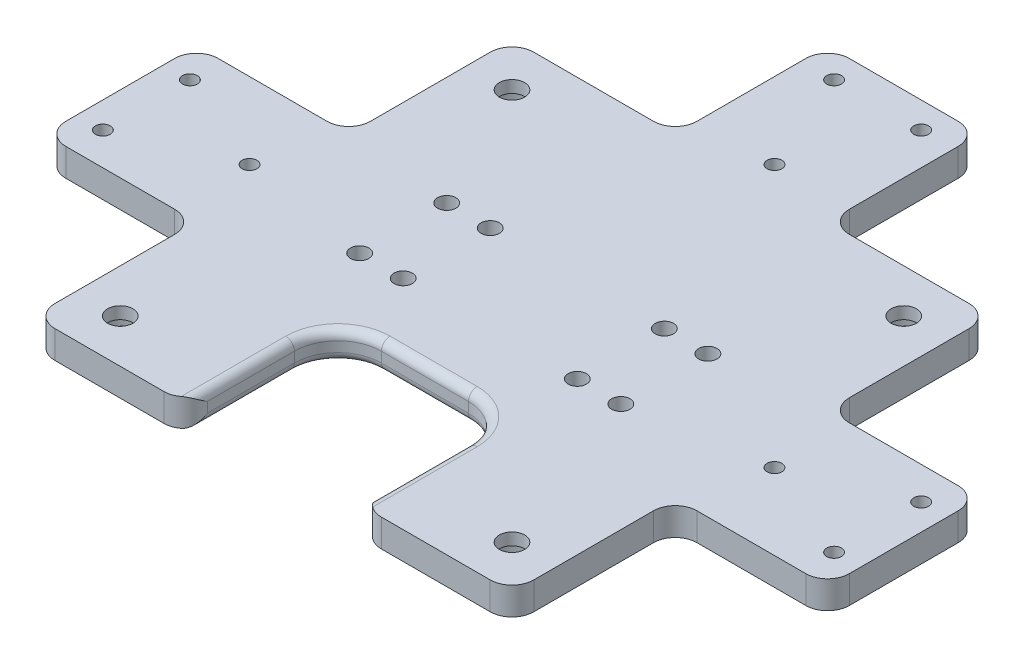
SolidWorks part; units mm, degrees
ref_plane "Front Plane" through (0, 0, 0) normal (0, 0, 1) x (1, 0, 0)
ref_plane "Top Plane" through (0, 0, 0) normal (0, 1, 0) x (1, 0, 0)
ref_plane "Right Plane" through (0, 0, 0) normal (1, 0, 0) x (0, 0, -1)
sketch "Base plate" plane through (0, 0, 0) normal (0, 1, 0) x (1, 0, 0)
  line L0 (55, -55) -> (-55, -55)
  line L5 (17.5, 55) -> (17.5, 90)
  line L6 (55, 55) -> (17.5, 55)
  line L7 (-55, -55) -> (-55, -17.5)
  line L8 (-55, -17.5) -> (-90, -17.5)
  line L9 (-90, -17.5) -> (-90, 17.5)
  line L10 (-90, 17.5) -> (-55, 17.5)
  line L11 (-55, 17.5) -> (-55, 55)
  line L12 (-55, 55) -> (-17.5, 55)
  line L13 (-17.5, 55) -> (-17.5, 90)
  line L14 (-17.5, 90) -> (17.5, 90)
  line L15 (0, 90) -> (0, -55) construction
  line L16 (55, 17.5) -> (55, 55)
  line L17 (90, 17.5) -> (55, 17.5)
  line L18 (90, -17.5) -> (90, 17.5)
  line L19 (55, -17.5) -> (90, -17.5)
  line L20 (55, -55) -> (55, -17.5)
  point P0 (0, 0)
  point P2 (90, 0)
  dimension "D1" = 55
  dimension "D2" = 55
  dimension "D7" = 90
  dimension "D3" = 55
  dimension "D6" = 17.5
  dimension "D4" = 35
  dimension "D5" = 35
extrude "Boss-Extrude1" add sketch "Base plate" along normal blind 6.35
hole_wizard "M5x0.8 Tapped Hole1" positions "Sketch10" profile "Sketch11" tap size "M5x0.8" standard "ANSI Metric" end condition through all
sketch "Sketch10" plane through (0, 0, 0) normal (0, -1, 0) x (-1, 0, 0)
  point P0 (-20, 15)
  point P2 (20, 15)
  point P4 (20, -5)
  point P6 (-20, -5)
  point P10 (-30, 15)
  point P12 (-30, -5)
  point P14 (30, 15)
  point P16 (30, -5)
  dimension "D1" = 40
  dimension "D2" = 20
  dimension "D3" = 15
  dimension "D4" = 20
  dimension "D5" = 60
  dimension "D6" = 30
sketch "Sketch11" plane through (20, 0, -15) normal (1, 0, 0) x (0, 0, -1)
  line L0 (0, 0) -> (0, 6.35)
  line L1 (0, 6.35) -> (2.1, 6.35)
  line L2 (2.1, 6.35) -> (2.1, 0)
  line L5 (2.1, 0) -> (0, 0)
  line L11 (0, -6.35) -> (0, 107.95) construction
  dimension "Thru Tap Drill Dia." = 4.2
  dimension "Thru Tap Drill Depth" = 6.35
cosmetic thread "Hole Thread1" parameters "D2"=5
cosmetic thread "Hole Thread2" parameters "D2"=5
cosmetic thread "Hole Thread3" parameters "D2"=5
cosmetic thread "Hole Thread4" parameters "D2"=5
cosmetic thread "Hole Thread5" parameters "D2"=5
cosmetic thread "Hole Thread6" parameters "D2"=5
cosmetic thread "Hole Thread7" parameters "D2"=5
cosmetic thread "Hole Thread8" parameters "D2"=5
sketch "Sketch4" plane through (0, 6.35, 0) normal (0, 1, 0) x (1, 0, 0)
  line L0 (-20, -55) -> (-20, -20)
  line L1 (-55, -55) -> (55, -55) construction
  line L2 (-20, -20) -> (20, -20)
  line L3 (20, -20) -> (20, -55)
  line L4 (20, -55) -> (-20, -55)
  point P4 (0, -55)
  point P8 (0, -55)
  dimension "D1" = 40
  dimension "D2" = 35
extrude "Cut-Extrude1" cut sketch "Sketch4" against normal through all
fillet "Fillet1" radius 5 18 edges at (55, 3.175, -17.5) (17.5, 3.175, -55) (17.5, 3.175, -90) (90, 3.175, -17.5) (55, 3.175, -55) (55, 3.175, 17.5) (90, 3.175, 17.5) (55, 3.175, 55) (-55, 3.175, 55) (-90, 3.175, 17.5) (-90, 3.175, -17.5) (-55, 3.175, -17.5) (-55, 3.175, -55) (-17.5, 3.175, -55) (-17.5, 3.175, -90) (-55, 3.175, 17.5) (20, 3.175, 55) (-20, 3.175, 55)
hole_wizard "CBORE for M5 Hex Head Bolt1" positions "Sketch2" profile "Sketch3" counterbore size "M5" standard "ANSI Metric" end condition through all
sketch "Sketch2" plane through (0, 0, 0) normal (0, 1, 0) x (1, 0, 0)
  line L0 (0, 76.3058) -> (0, -76.3058) construction
  line L4 (60, 0) -> (-60, 0) construction
  point P15 (-45, 45)
  point P19 (45, 45)
  point P22 (45, -45)
  point P23 (-45, -45)
  point P30 (0, 0)
  point P31 (0, 0)
  dimension "D1" = 45
  dimension "D2" = 45
sketch "Sketch3" plane through (-45, 0, 45) normal (1, 0, 0) x (0, 0, -1)
  line L0 (0, 0) -> (0, 6.35)
  line L1 (0, 6.35) -> (2.9, 6.35)
  line L3 (2.9, 6.35) -> (2.9, 3.58)
  line L4 (2.9, 3.58) -> (6.12, 3.58)
  line L5 (6.12, 3.58) -> (6.12, 0)
  line L7 (6.12, 0) -> (0, 0)
  line L11 (0, -6.35) -> (0, 107.95) construction
  dimension "Thru Hole Dia." = 5.8
  dimension "Thru Hole Depth" = 6.35
  dimension "C'Bore Dia." = 12.24
  dimension "C'Bore Depth" = 3.58
sketch "Sketch5" plane through (0, 0, 0) normal (0, 1, 0) x (1, 0, 0)
  line L0 (-101.5196, 0.1307) -> (-95.4419, 34.599)
  line L1 (-95.4419, 34.599) -> (-17.5, 90)
  line L2 (-17.5, 90) -> (17.5, 90)
  line L3 (17.5, 90) -> (95.4419, 34.599)
  line L4 (95.4419, 34.599) -> (101.5196, 0.1307)
  line L5 (101.5196, 0.1307) -> (46.553, -47.5537)
  line L6 (40, -50) -> (15, -50)
  line L7 (15, -50) -> (15, -15)
  line L8 (15, -15) -> (-15, -15)
  line L9 (-15, -15) -> (-15, -50)
  line L10 (-15, -50) -> (-40, -50)
  line L11 (-46.553, -47.5537) -> (-101.5196, 0.1307)
  line L12 (-3.4925, 0) -> (3.4925, 0) construction
  line L13 (0, 0) -> (0, 180) construction
  line L14 (-98.4808, 17.3648) -> (0, 0) construction
  arc A0 (-46.553, -47.5537) -> (-40, -50) centre (-40, -40) ccw
  arc A2 (46.553, -47.5537) -> (40, -50) centre (40, -40) cw
  point P25 (0, 90)
  dimension "D7" = 35
  dimension "D1" = 50
  dimension "D2" = 90
  dimension "D3" = 35
  dimension "D4" = 80
  dimension "D5" = 100
  dimension "D6" = 30
  dimension "D8" = 15
  dimension "D9" = 40
  dimension "D10" = 40
extrude "Boss-Extrude2" [suppressed] add sketch "Sketch5" along normal blind 6.35 separate body
fillet "Fillet2" radius 10 2 edges at (20, 3.175, 20) (-20, 3.175, 20)
fillet "Fillet3" radius 2 6 edges at (20, 6.35, 40) (0, 6.35, 20) (-20, 6.35, 40) (-20, 0, 40) (20, 0, 40) (0, 0, 20)
sketch "Sketch12" [suppressed] plane through (0, 0, 0) normal (0, -1, 0) x (1, 0, 0)
  line L0 (72.5, 60.3) -> (72.5, 84) construction
  line L1 (82.5, 84) -> (62.5, 84) construction
  line L2 (55, 90) -> (90, 90) construction
  line L3 (0, 0) -> (70.794, 0) construction
  line L4 (0, 0) -> (0, -42.7003) construction
  point P0 (82.5, 84)
  point P1 (62.5, 84)
  point P2 (72.5, 60.3)
  point P7 (82.5, -84)
  point P8 (62.5, -84)
  point P9 (72.5, 84)
  point P10 (72.5, -60.3)
  point P11 (-72.5, -60.3)
  point P15 (72.5, 90)
  point P19 (-62.5, -84)
  point P20 (-82.5, -84)
  point P21 (-72.5, 60.3)
  point P22 (-62.5, 84)
  point P23 (-82.5, 84)
  dimension "D1" = 20
  dimension "D2" = 6
  dimension "D3" = 23.7
hole_wizard "CBORE for M3 SHCS1" positions "Sketch6" profile "Sketch7" counterbore size "M3" standard "ANSI Metric" end condition through all
sketch "Sketch6" plane through (0, 0, 0) normal (0, -1, 0) x (-1, 0, 0)
  line L17 (0, 0) -> (0, 54.5385) construction
  line L18 (-84, 10) -> (-84, -10) construction
  line L20 (-60.3, 0) -> (-84, 0) construction
  line L24 (-90, -12.5) -> (-90, 12.5) construction
  line L26 (10, 84) -> (-10, 84) construction
  line L28 (-12.5, 90) -> (12.5, 90) construction
  line L29 (0, 60.3) -> (0, 84) construction
  point P0 (10, 84)
  point P2 (-10, 84)
  point P5 (0, 60.3)
  point P8 (-84, 10)
  point P10 (-84, -10)
  point P13 (-60.3, 0)
  point P126 (84, -10)
  point P127 (84, 10)
  point P128 (60.3, 0)
  point P142 (0, 84)
  dimension "D1" = 23.7
  dimension "D2" = 20
  dimension "D5" = 6
  dimension "D7" = 20
  dimension "D8" = 23.7
  dimension "D9" = 6
sketch "Sketch7" plane through (-10, 0, -84) normal (1, 0, 0) x (0, 0, -1)
  line L0 (0, 0) -> (0, 6.35)
  line L1 (0, 6.35) -> (1.7, 6.35)
  line L3 (1.7, 6.35) -> (1.7, 3)
  line L4 (1.7, 3) -> (3.25, 3)
  line L5 (3.25, 3) -> (3.25, 0)
  line L7 (3.25, 0) -> (0, 0)
  line L11 (0, -6.35) -> (0, 107.95) construction
  dimension "Thru Hole Dia." = 3.4
  dimension "Thru Hole Depth" = 6.35
  dimension "C'Bore Dia." = 6.5
  dimension "C'Bore Depth" = 3
hole_wizard "CBORE for M3 SHCS2" [suppressed] positions "3DSketch1" profile "Sketch13" counterbore size "M3" standard "ANSI Metric"
sketch3d "3DSketch1"
  point P1 (72.5, 0, 60.3)
  point P3 (82.5, 0, 84)
  point P5 (62.5, 0, 84)
  point P7 (-82.5, 0, 84)
  point P9 (-62.5, 0, 84)
  point P11 (-72.5, 0, 60.3)
  point P13 (-72.5, 0, -60.3)
  point P15 (-82.5, 0, -84)
  point P17 (-62.5, 0, -84)
  point P19 (72.5, 0, -60.3)
  point P21 (62.5, 0, -84)
  point P23 (82.5, 0, -84)
sketch "Sketch13" plane through (72.5, 0, 60.3) normal (1, 0, 0) x (0, 0, -1)
  line L0 (0, 0) -> (0, 6.35)
  line L1 (0, 6.35) -> (1.7, 6.35)
  line L3 (1.7, 6.35) -> (1.7, 3)
  line L4 (1.7, 3) -> (3.25, 3)
  line L5 (3.25, 3) -> (3.25, 0)
  line L7 (3.25, 0) -> (0, 0)
  line L11 (0, -6.35) -> (0, 107.95) construction
  dimension "Thru Hole Dia." = 3.4
  dimension "Thru Hole Depth" = 6.35
  dimension "C'Bore Dia." = 6.5
  dimension "C'Bore Depth" = 3
equation "\"D5@Base plate\" = \"Branch_length\""
